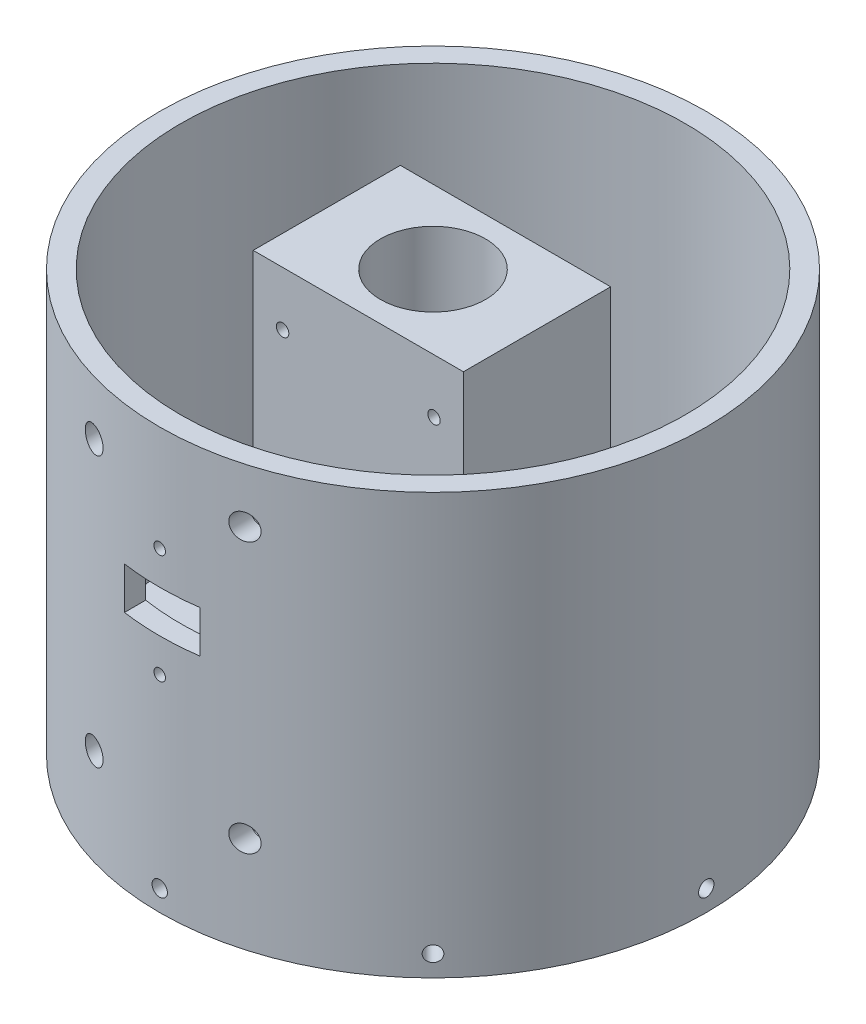
SolidWorks part; units mm, degrees
note: The reader was unsure of these and kept them because the rebuilt part matched: shared geometry of "Sketch1<5>", "Sketch1<6>", "Sketch11<6>".
other "Markup1"
sketch "Sketch37" plane through (49.25, 100, -49.25) normal (0.0642, 0.4256, -0.9026) x (-0.9466, -0.2605, -0.1902)
sketch "Sketch38" plane through (49.25, 100, -49.25) normal (0.0642, 0.4256, -0.9026) x (-0.9466, -0.2605, -0.1902)
sketch "Sketch41" plane through (49.25, 100, -49.25) normal (0.0642, 0.4256, -0.9026) x (-0.9466, -0.2605, -0.1902)
ref_plane "Front Plane" through (0, 0, 0) normal (0, 0, 1) x (1, 0, 0)
ref_plane "Top Plane" through (0, 0, 0) normal (0, 1, 0) x (1, 0, 0)
ref_plane "Right Plane" through (0, 0, 0) normal (1, 0, 0) x (0, 0, -1)
sketch "Sketch1" plane through (0, 0, 0) normal (0, 1, 0) x (1, 0, 0)
  line L0 (12.5, 0) -> (13, 0)
  line L1 (24.7396, 17.5) -> (-25.2604, 17.5)
  line L3 (24.7396, 17.5) -> (24.7396, -17.5)
  line L4 (24.7396, -17.5) -> (-25.2604, -17.5)
  line L5 (-25.2604, 17.5) -> (-25.2604, -17.5)
  line L6 (-12.5, 0) -> (-13, 0)
  circle A1 centre (0, 0) radius 65
  circle A2 centre (0, 0) radius 12.5
  circle A3 centre (0, 0) radius 13
  circle A4 centre (0, 0) radius 17.5
  circle A5 centre (0, 0) radius 60
  dimension "D1" = 25
  dimension "D2" = 120
  dimension "D3" = 26
  dimension "D4" = 35
  dimension "D5" = 130
  dimension "D6" = 50
extrude "Boss-Extrude1" add sketch "Sketch1" along normal blind 100 contours A4 A3 L3 | A2
extrude "Boss-Extrude2" add sketch "Sketch1<5>" along normal blind 10 contours A5 L5 L1 L3 L4
sketch "Sketch1<5>" plane through (0, 0, 0) normal (0, 1, 0) x (1, 0, 0) same geometry as "Sketch1"
extrude "Boss-Extrude3" add sketch "Sketch1<6>" along normal blind 100 contours A1 A5
sketch "Sketch1<6>" plane through (0, 0, 0) normal (0, 1, 0) x (1, 0, 0) same geometry as "Sketch1"
sketch "Sketch3" plane through (0, 0, -17.5) normal (0, 0, -1) x (-1, 0, 0)
  line L0 (-24.7396, 100) -> (25.2604, 100) construction
  line L1 (-19.2396, 88.625) -> (19.7604, 88.625)
  line L2 (-19.2396, 88.625) -> (-19.2396, 21.375)
  line L3 (-19.2396, 21.375) -> (19.7604, 21.375)
  line L4 (19.7604, 88.625) -> (19.7604, 21.375)
  line L5 (19.7604, 87.125) -> (18.2604, 87.125)
  line L6 (-24.7396, 100) -> (-24.7396, 10) construction
  line L7 (18.2604, 87.125) -> (18.2604, 88.625)
  line L8 (18.2604, 21.375) -> (18.2604, 22.875)
  line L9 (18.2604, 22.875) -> (19.7604, 22.875)
  line L10 (-19.2396, 88.625) -> (-17.7396, 88.625)
  line L11 (-19.2396, 88.625) -> (-19.2396, 87.125)
  line L12 (-19.2396, 87.125) -> (-17.7396, 87.125)
  line L13 (-17.7396, 88.625) -> (-17.7396, 87.125)
  line L14 (-17.7396, 21.375) -> (-17.7396, 22.875)
  line L15 (-17.7396, 22.875) -> (-19.2396, 22.875)
  line L17 (-9, 67) -> (-9, 57)
  line L22 (-9, 57) -> (9, 57)
  line L23 (9, 57) -> (9, 67)
  line L24 (9, 67) -> (-9, 67)
  line L25 (0, 100) -> (0, 0) construction
  dimension "D1" = 39
  dimension "D2" = 67.25
  dimension "D3" = 11.375
  dimension "D4" = 5.5
  dimension "D5" = 1.5
  dimension "D6" = 1.5
  dimension "D7" = 18
  dimension "D8" = 10
  dimension "D9" = 9
sketch "Sketch11" plane through (0, 0, -17.5) normal (0, 0, -1) x (-1, 0, 0)
  line L0 (0.2782, 97.0305) -> (0.2782, 15.242)
  line L1 (0.2782, 56.1363) -> (22.1947, 56.1363)
  line L2 (25.2604, 100) -> (25.2604, 10) construction
  line L3 (-19.6443, 66.1363) -> (-24.704, 66.1363)
  line L4 (20.2007, 56.1363) -> (25.2604, 56.1363)
  line L5 (20.2007, 46.1363) -> (20.2007, 66.1363)
  line L6 (20.2007, 66.1363) -> (25.2604, 66.1363)
  line L7 (25.2604, 46.1363) -> (25.2604, 66.1363)
  line L8 (-24.704, 46.1363) -> (-24.704, 66.1363)
  line L9 (-19.6443, 56.1363) -> (-24.704, 56.1363)
  line L10 (-19.6443, 46.1363) -> (-19.6443, 66.1363)
  line L11 (20.2007, 46.1363) -> (25.2604, 46.1363)
  line L12 (-19.6443, 46.1363) -> (-24.704, 46.1363)
  line L13 (-14.7218, 21.0751) -> (-14.7218, 13.0751)
  line L14 (-14.7218, 21.0751) -> (15.2782, 21.0751)
  line L15 (0.2782, 21.0751) -> (0.2782, 13.0751)
  line L16 (-14.7218, 13.0751) -> (15.2782, 13.0751)
  line L17 (15.2782, 21.0751) -> (15.2782, 13.0751)
  line L18 (-14.7218, 89.0305) -> (-14.7218, 97.0305)
  line L19 (-14.7218, 89.0305) -> (15.2782, 89.0305)
  line L20 (0.2782, 89.0305) -> (0.2782, 97.0305)
  line L21 (-14.7218, 97.0305) -> (15.2782, 97.0305)
  line L22 (15.2782, 89.0305) -> (15.2782, 97.0305)
  line L24 (-14.7218, 89.0305) -> (15.2782, 89.0305)
  line L25 (-14.7218, 89.0305) -> (-14.7218, 92.0305)
  line L26 (-14.7218, 92.0305) -> (15.2782, 92.0305)
  line L27 (15.2782, 89.0305) -> (15.2782, 92.0305)
  line L28 (-14.7218, 21.0751) -> (15.2782, 21.0751)
  line L29 (-14.7218, 21.0751) -> (-14.7218, 18.0751)
  line L30 (-14.7218, 18.0751) -> (15.2782, 18.0751)
  line L31 (15.2782, 21.0751) -> (15.2782, 18.0751)
  circle A0 centre (-17.7396, 87.125) radius 2
  circle A1 centre (18.2604, 87.125) radius 2
  circle A2 centre (18.2604, 22.875) radius 2
  circle A3 centre (-17.7396, 22.875) radius 2
  circle A4 centre (-17.7396, 87.125) radius 1.475
  circle A5 centre (18.2604, 87.125) radius 1.475
  circle A6 centre (-17.7396, 22.875) radius 1.475
  circle A7 centre (18.2604, 22.875) radius 1.475
  circle A8 centre (-17.7396, 87.125) radius 3
  circle A9 centre (-17.7396, 22.875) radius 3
  circle A10 centre (18.2604, 22.875) radius 3
  circle A11 centre (18.2604, 87.125) radius 3
  dimension "D1" = 10
  dimension "D8" = 2.95
  dimension "D9" = 2.95
  dimension "D10" = 2.95
  dimension "D11" = 2.95
  dimension "D12" = 6
  dimension "D13" = 6
  dimension "D14" = 6
  dimension "D15" = 6
  dimension "D2" = 15
  dimension "D3" = 8
  dimension "D4" = 8
  dimension "D5" = 15
  dimension "D6" = 3
  dimension "D7" = 3
extrude "Boss-Extrude4" add sketch "Sketch11" along normal blind 2
sketch "Sketch19" plane through (0, 0, 17.5) normal (0, 0, 1) x (1, 0, 0)
  line L0 (24.7396, 100) -> (24.7396, 10) construction
  line L1 (-15.2604, 83.9821) -> (14.7396, 83.9821)
  line L2 (-15.2604, 83.9821) -> (-15.2604, 27.9821)
  line L3 (-15.2604, 27.9821) -> (14.7396, 27.9821)
  line L4 (14.7396, 83.9821) -> (14.7396, 27.9821)
  line L5 (-25.2604, 100) -> (-25.2604, 10) construction
  line L6 (-15.2604, 33.6576) -> (-20.2604, 33.6576)
  line L7 (-20.2604, 33.6576) -> (-20.2604, 23.6576)
  line L8 (-20.2604, 23.6576) -> (19.7396, 23.6576)
  line L9 (19.7396, 23.6576) -> (19.7396, 33.6576)
  line L10 (19.7396, 33.6576) -> (14.7396, 33.6576)
  line L11 (-15.2604, 55.9821) -> (14.7396, 55.9821)
  line L12 (-15.2604, 83.9821) -> (-20.2604, 83.9821)
  line L13 (-15.2604, 83.9821) -> (-15.2604, 73.9821)
  line L14 (-15.2604, 73.9821) -> (-20.2604, 73.9821)
  line L15 (-20.2604, 83.9821) -> (-20.2604, 73.9821)
  line L16 (14.7396, 83.9821) -> (19.7396, 83.9821)
  line L17 (14.7396, 83.9821) -> (14.7396, 73.9821)
  line L18 (14.7396, 73.9821) -> (19.7396, 73.9821)
  line L19 (19.7396, 83.9821) -> (19.7396, 73.9821)
  line L20 (-3.2604, 55.9821) -> (-3.2604, 52.9821)
  line L21 (-0.2604, 55.9821) -> (2.7396, 55.9821)
  line L22 (-0.2604, 55.9821) -> (-0.2604, 52.9821)
  line L23 (-3.2604, 52.9821) -> (2.7396, 52.9821)
  line L24 (2.7396, 55.9821) -> (2.7396, 52.9821)
  line L26 (-25.2604, 100) -> (-18.2604, 100)
  line L27 (-25.2604, 100) -> (-25.2604, 87.11)
  line L28 (-25.2604, 87.11) -> (-18.2604, 87.11)
  line L29 (-18.2604, 100) -> (-18.2604, 87.11)
  line L30 (-25.2604, 10) -> (-18.2604, 10)
  line L31 (-25.2604, 10) -> (-25.2604, 22.89)
  line L32 (-25.2604, 22.89) -> (-18.2604, 22.89)
  line L33 (-18.2604, 10) -> (-18.2604, 22.89)
  line L34 (24.7396, 100) -> (17.7396, 100)
  line L35 (24.7396, 100) -> (24.7396, 87.11)
  line L36 (24.7396, 87.11) -> (17.7396, 87.11)
  line L37 (17.7396, 100) -> (17.7396, 87.11)
  line L38 (24.7396, 10) -> (17.7396, 10)
  line L39 (24.7396, 10) -> (24.7396, 22.89)
  line L40 (24.7396, 22.89) -> (17.7396, 22.89)
  line L41 (17.7396, 10) -> (17.7396, 22.89)
  circle A0 centre (-18.2604, 87.11) radius 3
  circle A1 centre (-18.2604, 22.89) radius 3
  circle A2 centre (17.7396, 22.89) radius 3
  circle A3 centre (17.7396, 87.11) radius 3
  dimension "D13" = 6
  dimension "D20" = 6
  dimension "D21" = 6
  dimension "D22" = 6
  dimension "D1" = 30
  dimension "D2" = 56
  dimension "D3" = 10
  dimension "D4" = 10
  dimension "D5" = 10
  dimension "D6" = 5
  dimension "D7" = 40
  dimension "D8" = 10
  dimension "D9" = 3
  dimension "D10" = 3
  dimension "D11" = 12.89
  dimension "D12" = 7
  dimension "D14" = 7
  dimension "D15" = 12.89
  dimension "D16" = 7
  dimension "D17" = 12.89
  dimension "D18" = 12.89
  dimension "D19" = 7
ref_plane "Plane1" through (0, 0, 0) normal (0, 1, 0) x (1, 0, 0)
ref_plane "Plane2" through (0, 0, 0) normal (0, 0, 1) x (1, 0, 0)
ref_plane "Plane3" through (0, 0, 0) normal (-1, 0, 0) x (0, 0, 1)
sketch "Sketch30" plane through (0, 0, 0) normal (0, -1, 0) x (1, 0, 0)
  line L0 (0, 7.62) -> (0, 65)
  line L1 (0, 19.25) -> (0, -19.25) construction
  circle A0 centre (0, 0) radius 7.62 construction
  circle A1 centre (0, 0) radius 65 construction
ref_plane "Plane8" through (0, 0, 65) normal (-1, 0, 0) x (0, 0, 1)
sketch "Sketch32" plane through (0, 0, 65) normal (-1, 0, 0) x (0, 0, 1)
  line L0 (0, 0) -> (0, 5)
  line L1 (-57.38, 0) -> (0, 0) construction
  line L2 (0, 0) -> (0, 100) construction
ref_plane "Plane9" through (0, 0, 0) normal (-0.7071, 0, -0.7071) x (-0.7071, 0, 0.7071)
ref_plane "Plane10" through (0, 0, 0) normal (-0.7071, 0, 0.7071) x (0.7071, 0, 0.7071)
ref_plane "Plane11" through (0, 0, 0) normal (0, 0, 1) x (1, 0, 0)
extrude "Cut-Extrude1" cut sketch "Sketch3" against normal blind 30 from offset 70 offset against normal yes
extrude "Cut-Extrude2" cut sketch "Sketch11<6>" against normal blind 50 contours A5 | A6 | A4 | A7
sketch "Sketch11<6>" plane through (0, 0, -17.5) normal (0, 0, -1) x (-1, 0, 0) same geometry as "Sketch11"
ref_plane "Plane12" through (0, 0, 65) normal (0, 0, 1) x (1, 0, 0)
sketch "Sketch40" plane through (0, 0, 65) normal (0, 0, 1) x (1, 0, 0)
  line L0 (0, 0) -> (0, 5) construction
  line L1 (60, 10) -> (-60, 10) construction
  circle A0 centre (0, 5) radius 1.825
  dimension "D1" = 3.65
  dimension "D2" = 5
extrude "Cut-Extrude3" cut sketch "Sketch40" against normal blind 11 contours A0
pattern_circular "CirPattern1" count 8 over 360 about axis through (0, 0, 0) along (0, 1, 0) of "Cut-Extrude3"
sketch "Sketch42" plane through (0, 0, -19.5) normal (0, 0, -1) x (-1, 0, 0)
  circle A0 centre (-17.7396, 87.11) radius 3
  circle A1 centre (18.2604, 87.11) radius 3
  circle A2 centre (18.2604, 22.89) radius 3
  circle A3 centre (-17.7396, 22.89) radius 3
extrude "Cut-Extrude5" cut sketch "Sketch42" against normal blind 30 from offset 60 offset against normal yes
sketch "Sketch43" plane through (0, 0, 0) normal (0, -1, 0) x (1, 0, 0)
  line L1 (-34.0744, 50.855) -> (-27.865, 50.855)
  line L2 (-34.0744, 50.855) -> (-34.0744, 38.205)
  line L3 (-34.0744, 38.205) -> (-27.865, 38.205)
  line L4 (-27.865, 50.855) -> (-27.865, 38.205)
  line L5 (38.205, 34.0744) -> (50.855, 34.0744)
  line L6 (38.205, 34.0744) -> (38.205, 27.865)
  line L7 (38.205, 27.865) -> (50.855, 27.865)
  line L8 (50.855, 34.0744) -> (50.855, 27.865)
  line L9 (27.865, -38.205) -> (34.0744, -38.205)
  line L10 (27.865, -38.205) -> (27.865, -50.855)
  line L11 (27.865, -50.855) -> (34.0744, -50.855)
  line L12 (34.0744, -38.205) -> (34.0744, -50.855)
  line L13 (-38.205, -34.0744) -> (-50.855, -34.0744)
  line L14 (-38.205, -34.0744) -> (-38.205, -27.865)
  line L15 (-38.205, -27.865) -> (-50.855, -27.865)
  line L16 (-50.855, -34.0744) -> (-50.855, -27.865)
extrude "Cut-Extrude6" cut sketch "Sketch43" against normal blind 10
sketch "Sketch44" plane through (-56.9703, -4.6918, -98.6597) normal (0, 0, 1) x (1, 0, 0)
  circle A0 centre (56.9703, 79.6918) radius 1.375
  circle A1 centre (56.9703, 53.6918) radius 1.375
extrude "Cut-Extrude7" cut sketch "Sketch44" against normal blind 20 from offset 170
